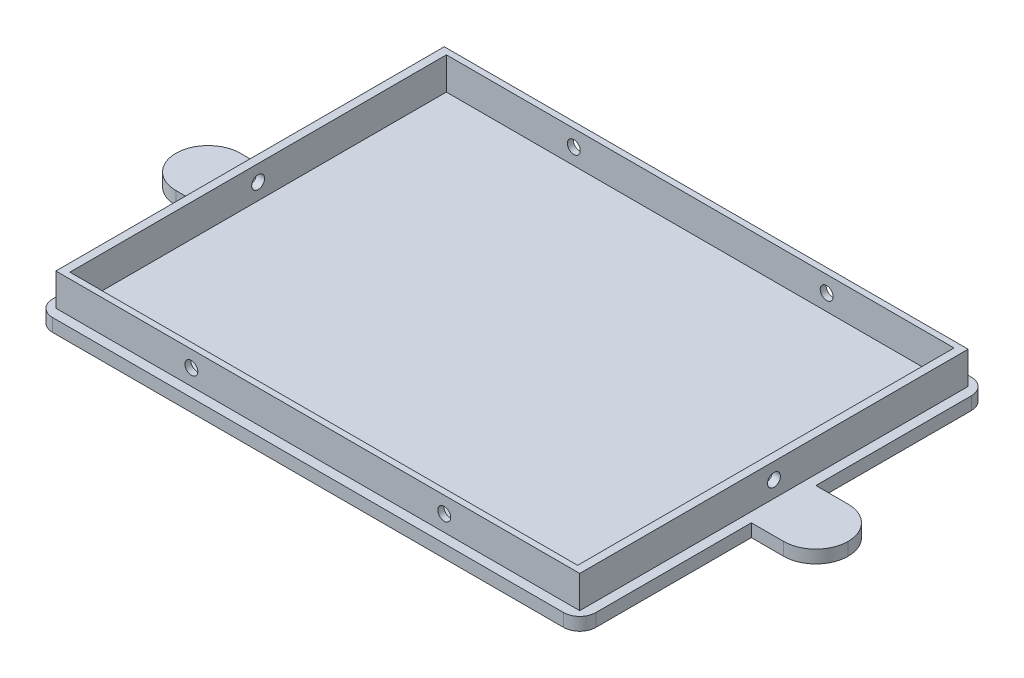
SolidWorks part; units mm, degrees
ref_plane "Front Plane" through (0, 0, 0) normal (0, 0, 1) x (1, 0, 0)
ref_plane "Top Plane" through (0, 0, 0) normal (0, 1, 0) x (1, 0, 0)
ref_plane "Right Plane" through (0, 0, 0) normal (1, 0, 0) x (0, 0, -1)
sketch "Sketch1" plane through (0, 0, 0) normal (0, 1, 0) x (1, 0, 0)
  line L1 (-84.19, 63.195) -> (84.19, 63.195)
  line L2 (-84.19, 63.195) -> (-84.19, 10)
  line L3 (-84.19, -63.195) -> (84.19, -63.195)
  line L4 (84.19, 63.195) -> (84.19, 10)
  line L5 (-84.19, 63.195) -> (84.19, -63.195) construction
  line L6 (-84.19, -63.195) -> (84.19, 63.195) construction
  line L7 (-84.19, 10) -> (-104.19, 10)
  line L8 (-104.19, 10) -> (-104.19, -10)
  line L9 (-104.19, -10) -> (-84.19, -10)
  line L10 (-84.19, -10) -> (-84.19, -63.195)
  line L11 (0, 81.5323) -> (0, -81.5323) construction
  line L12 (104.19, -10) -> (84.19, -10)
  line L13 (104.19, 10) -> (104.19, -10)
  line L14 (84.19, 10) -> (104.19, 10)
  line L15 (84.19, -10) -> (84.19, -63.195)
  point P0 (0, 0)
  point P9 (-84.19, 0)
  point P14 (0, 0)
  dimension "D1" = 168.38
  dimension "D2" = 126.39
  dimension "D3" = 20
  dimension "D4" = 20
extrude "Boss-Extrude1" add sketch "Sketch1" along normal blind 4
sketch "Sketch2" plane through (0, 4, 0) normal (0, 1, 0) x (1, 0, 0)
  line L0 (-84.19, 63.195) -> (-84.19, 10) construction
  line L1 (-81.19, 60.195) -> (81.19, 60.195)
  line L2 (-81.19, 60.195) -> (-81.19, -60.195)
  line L3 (-81.19, -60.195) -> (81.19, -60.195)
  line L4 (81.19, 60.195) -> (81.19, -60.195)
  line L5 (-81.19, 60.195) -> (81.19, -60.195) construction
  line L6 (-81.19, -60.195) -> (81.19, 60.195) construction
  line L7 (84.19, 63.195) -> (-84.19, 63.195) construction
  line L10 (-78.69, 58.3415) -> (78.69, 58.3415)
  line L11 (-78.69, 58.3415) -> (-78.69, -58.3415)
  line L12 (-78.69, -58.3415) -> (78.69, -58.3415)
  line L13 (78.69, 58.3415) -> (78.69, -58.3415)
  line L14 (-78.69, 58.3415) -> (78.69, -58.3415) construction
  line L15 (-78.69, -58.3415) -> (78.69, 58.3415) construction
  point P0 (0, 0)
  point P10 (0, 0)
  dimension "D1" = 3
  dimension "D2" = 3
  dimension "D3" = 2.5
extrude "Boss-Extrude2" add sketch "Sketch2" along normal blind 10
fillet "Fillet1" radius 10 4 edges at (104.19, 2, -10) (104.19, 2, 10) (-104.19, 2, -10) (-104.19, 2, 10)
fillet "Fillet2" radius 5 4 edges at (-84.19, 2, -63.195) (84.19, 2, -63.195) (84.19, 2, 63.195) (-84.19, 2, 63.195)
sketch "Sketch3" plane through (81.19, 0, 0) normal (1, 0, 0) x (0, 0, -1)
  line L0 (10, 4) -> (58.195, 4) construction
  circle A0 centre (0, 9) radius 2
  point P2 (0, 0)
  dimension "D1" = 5
extrude "Cut-Extrude1" cut sketch "Sketch3" against normal blind 182
sketch "Sketch4" plane through (0, 0, -63.195) normal (0, 0, -1) x (-1, 0, 0)
  line L0 (-81.19, 4) -> (81.19, 4) construction
  line L1 (79.19, 0) -> (79.19, 4) construction
  line L2 (-79.19, 4) -> (-79.19, 0) construction
  circle A0 centre (39.19, 9) radius 2
  circle A1 centre (-39.19, 9) radius 2
  dimension "D1" = 5
  dimension "D2" = 5
  dimension "D3" = 40
  dimension "D4" = 40
extrude "Cut-Extrude2" cut sketch "Sketch4" against normal blind 182
